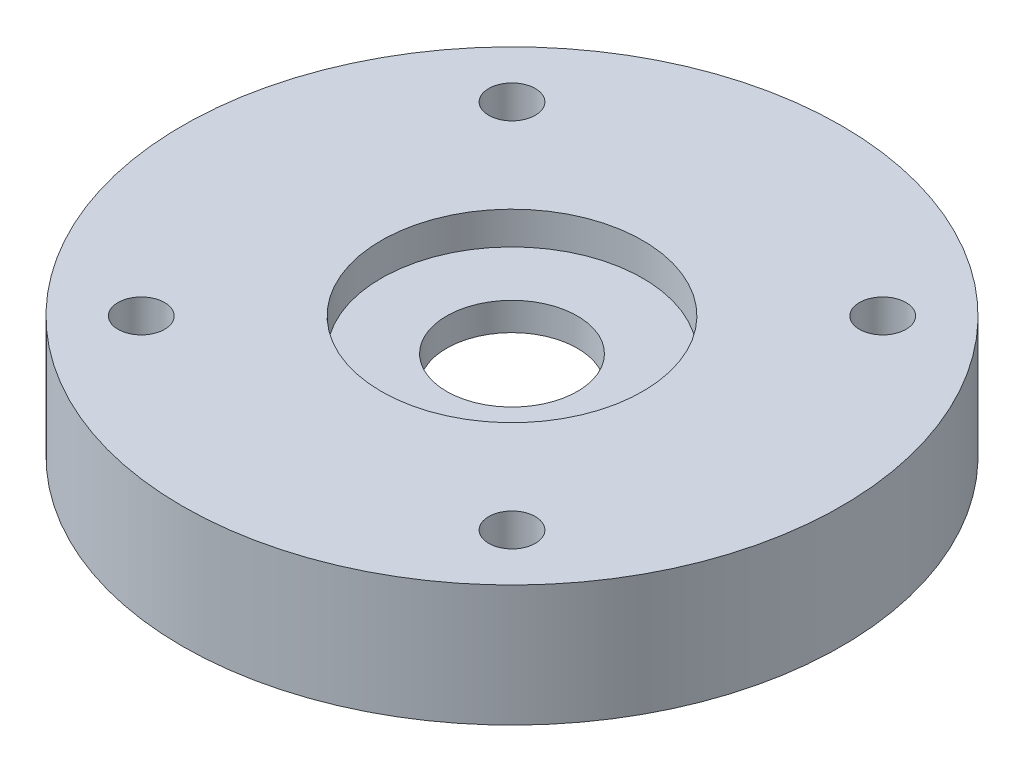
SolidWorks part; units mm, degrees
ref_plane "Front Plane" through (0, 0, 0) normal (0, 0, 1) x (1, 0, 0)
ref_plane "Top Plane" through (0, 0, 0) normal (0, 1, 0) x (1, 0, 0)
ref_plane "Right Plane" through (0, 0, 0) normal (1, 0, 0) x (0, 0, -1)
sketch "Sketch2" plane through (0, 0, 0) normal (0, 1, 0) x (1, 0, 0)
  line L0 (-9.017, 4.1927) -> (-9.017, -4.1927)
  line L1 (9.017, 4.1927) -> (9.017, -4.1927)
  circle A0 centre (0, 0) radius 9.9441
  circle A1 centre (0, 0) radius 16.002
  dimension "D1" = 19.8882
  dimension "D2" = 32.004
  dimension "D3" = 18.034
extrude "Boss-Extrude2" add sketch "Sketch2" along normal blind 5.8928 contours L1 A0 | L0 A0 | L1 A0 L0 | A1 A0 L1 region at (0, 0, 0) region at (-9.3894, 0, 0) region at (9.3894, 0, 0) region at (-15.5494, 0, 0)
extrude "Cut-Extrude1" cut sketch "Sketch2<3>" along normal blind 2.9464 contours L1 A0 L0 region at (0, 0, 0)
sketch "Sketch2<3>" plane through (0, 0, 0) normal (0, 1, 0) x (1, 0, 0) same geometry as "Sketch2"
sketch "Sketch3" plane through (0, 0, 0) normal (0, -1, 0) x (1, 0, 0)
  line L0 (-9, 9) -> (9, -9)
  line L1 (-9, -9) -> (9, -9)
  line L2 (-9, -9) -> (-9, 9)
  line L3 (-9, 9) -> (9, 9)
  line L4 (9, -9) -> (9, 9)
  circle A0 centre (0, 0) radius 3.175
  point P4 (0, 0)
  dimension "D3" = 6.35
  dimension "D1" = 18
  dimension "D2" = 18
hole_wizard "#4-40 Tapped Hole1" positions "3DSketch1" profile "Sketch4" tap size "#4-40" standard "ANSI Inch" end condition through all
sketch3d "3DSketch1"
  point P0 (-9, 0, 9)
  point P3 (9, 0, 9)
  point P6 (9, 0, -9)
  point P9 (-9, 0, -9)
sketch "Sketch4" plane through (-9, 0, 9) normal (1, 0, 0) x (0, 0, -1)
  line L0 (0, 0) -> (0, 5.8928)
  line L1 (0, 5.8928) -> (1.1303, 5.8928)
  line L2 (1.1303, 5.8928) -> (1.1303, 0)
  line L5 (1.1303, 0) -> (0, 0)
  line L11 (0, -6.35) -> (0, 107.95) construction
  dimension "Thru Tap Drill Dia." = 2.2606
  dimension "Thru Tap Drill Depth" = 5.8928
cosmetic thread "Hole Thread1" parameters "D2"=2.8448
cosmetic thread "Hole Thread2" parameters "D2"=2.8448
cosmetic thread "Hole Thread3" parameters "D2"=2.8448
cosmetic thread "Hole Thread4" parameters "D2"=2.8448
extrude "Cut-Extrude2" cut sketch "Sketch3" against normal through all contours L0 A0 | L0 A0 region at (0.9528, 0, 0.9528) region at (-0.9528, 0, -0.9528)
sketch "Sketch5" plane through (0, 5.8928, 0) normal (0, 1, 0) x (1, 0, 0)
  circle A0 centre (0, 0) radius 6.35
  dimension "D1" = 12.7
extrude "Cut-Extrude3" cut sketch "Sketch5" against normal blind 1.5875
